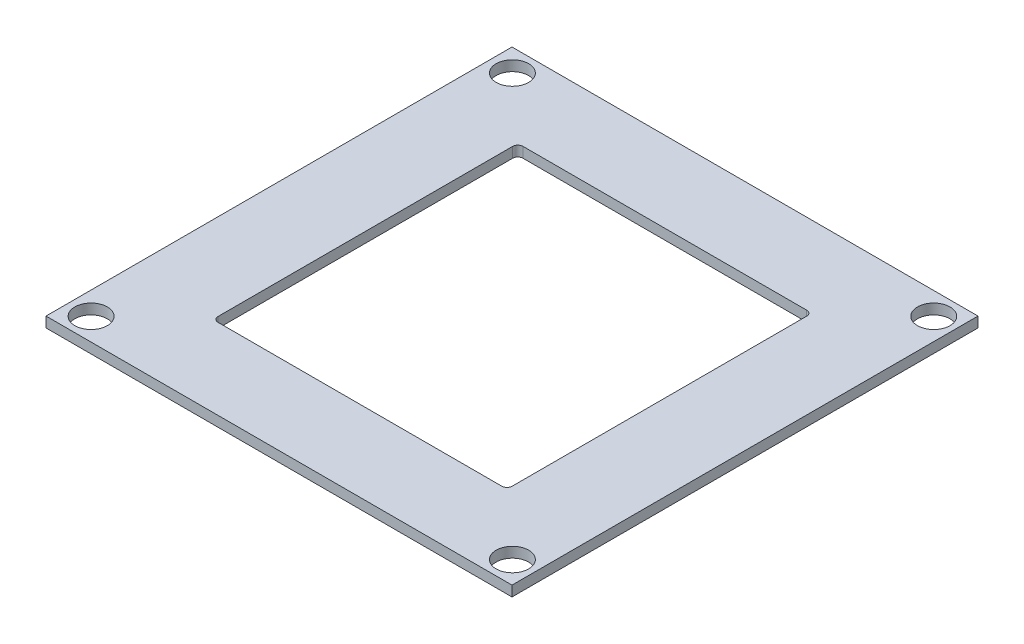
SolidWorks part; units mm, degrees
material "Acrylic (Medium-high impact)"
ref_plane "Front" through (0, 0, 0) normal (0, 0, 1) x (1, 0, 0)
ref_plane "Top" through (0, 0, 0) normal (0, 1, 0) x (1, 0, 0)
ref_plane "Right" through (0, 0, 0) normal (1, 0, 0) x (0, 0, -1)
sketch "Sketch1" plane through (0, 0, 0) normal (0, 1, 0) x (1, 0, 0)
  line L1 (0, -143.396) -> (286.792, -143.396)
  line L2 (0, -143.396) -> (0, 143.396)
  line L3 (0, 143.396) -> (286.792, 143.396)
  line L4 (286.792, -143.396) -> (286.792, 143.396)
  point P6 (0, 0)
  dimension "D1" = 286.792
  dimension "D2" = 286.792
extrude "Boss-Extrude1" add sketch "Sketch1" along normal blind 6.35
other "PropertyManager"
sketch "Sketch2" plane through (0, 0, 0) normal (0, -1, 0) x (1, 0, 0)
  line L0 (230.9625, -90.6462) -> (56.3375, 90.6462) construction
  line L2 (234.14, 93.8237) -> (53.16, 93.8237)
  line L3 (234.14, 93.8237) -> (234.14, -93.8237)
  line L4 (234.14, -93.8237) -> (53.16, -93.8237)
  line L5 (53.16, 93.8237) -> (53.16, -93.8237)
  line L6 (234.14, 93.8237) -> (53.16, -93.8237) construction
  line L7 (234.14, -93.8237) -> (53.16, 93.8237) construction
  circle A0 centre (273.3, -129.65) radius 10
  circle A1 centre (14, -129.65) radius 10
  circle A2 centre (14, 129.65) radius 10
  circle A3 centre (273.3, 129.65) radius 10
  arc A4 (53.1625, -92.6987) -> (54.285, -93.8213) centre (53.7213, -93.2625) ccw construction
  point P16 (143.65, 0)
extrude "Cut-Extrude1" cut sketch "Sketch2" against normal blind 6.35
fillet "Fillet1" radius 3.175 4 edges at (53.16, 3.175, -93.8237) (234.14, 3.175, -93.8237) (234.14, 3.175, 93.8237) (53.16, 3.175, 93.8237)
equation "\"thick\"= .25in"
equation "\"tol\"= .01"
equation "\"ftprnt\"= 30cm"
equation "\"D1@Sketch1\"    = \"ftprnt\"-(\"thick\"*2)-(\"tol\"*2)"
equation "\"D1@Boss-Extrude1\"=\"thick\""
equation "\"height\"= 5cm"
equation "\"D2@Sketch1\"    = \"ftprnt\"-(\"thick\"*2)-(\"tol\"*2)"
